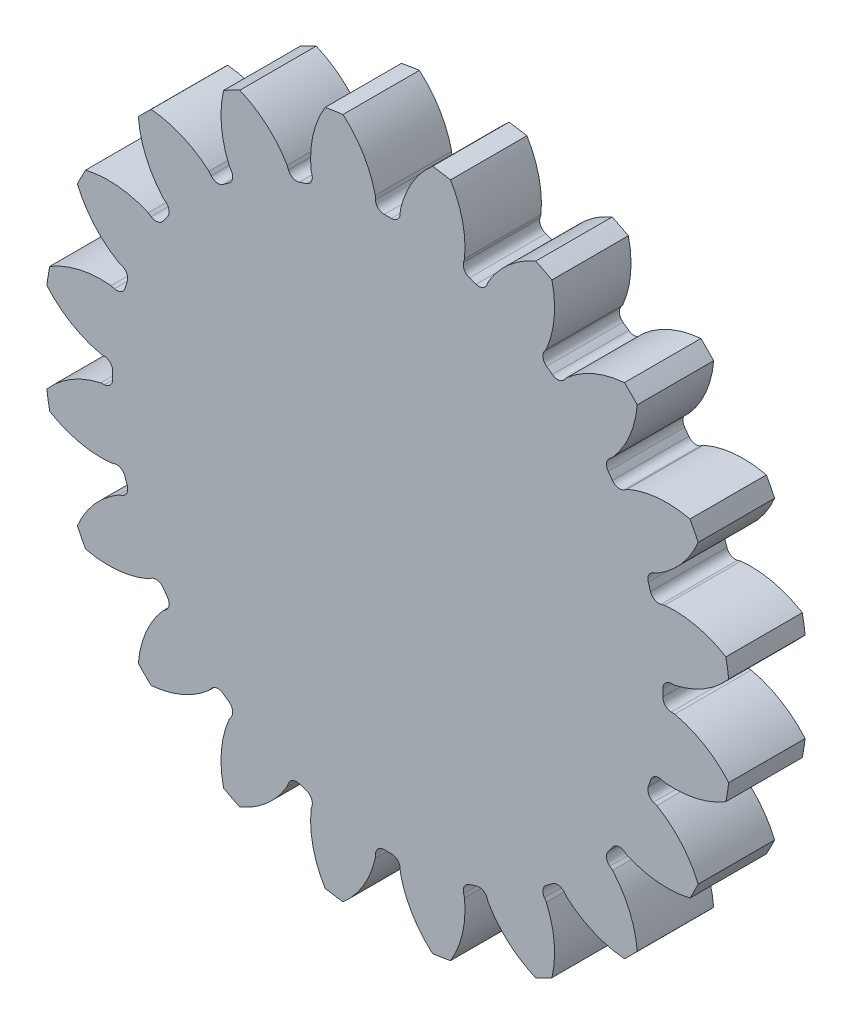
SolidWorks part; units mm, degrees
ref_plane "前视基准面" through (0, 0, 0) normal (0, 0, 1) x (1, 0, 0)
ref_plane "上视基准面" through (0, 0, 0) normal (0, 1, 0) x (1, 0, 0)
ref_plane "右视基准面" through (0, 0, 0) normal (1, 0, 0) x (0, 0, -1)
sketch "Sketch1" plane through (0, 0, 0) normal (0, 0, 1) x (1, 0, 0)
  line L0 (0, 0) -> (0, 22.5) construction
  line L1 (0.8204, 18.7759) -> (0, 0) construction
  line L2 (0, 0) -> (7.1927, 17.363) construction
  line L3 (0.8204, 18.7759) -> (0.7857, 17.9828)
  line L4 (0, 0) -> (3.5198, 22.223) construction
  line L6 (-0.8204, 18.7759) -> (-0.7857, 17.9828)
  circle A0 centre (0, 0) radius 20 construction
  circle A2 centre (0, 0) radius 18 construction
  arc A3 (0.8204, 18.7759) -> (2.9326, 22.3081) centre (7.1927, 17.363) cw
  circle A4 centre (0, 0) radius 18.7939 construction
  arc A5 (-0.7857, 17.9828) -> (0.7857, 17.9828) centre (0, 0) cw
  arc A6 (-0.8204, 18.7759) -> (-2.9326, 22.3081) centre (-7.1927, 17.363) ccw
  circle A7 centre (0, 0) radius 22.5
  arc A8 (1.2061, 19.9636) -> (3.1287, 19.7538) centre (0, 0) cw construction
  dimension "Db" = 37.5877
  dimension "Da" = 45
  dimension "Dp" = 40
  dimension "Dd" = 36
  dimension "alpha" = 20
  dimension "deg_half" = 9
  dimension "s_half" = 1.9348
extrude "Df circle" add sketch "Sketch1" along normal mid plane 5 contours A7
extrude "one teeth" cut sketch "Sketch" against normal through all both and the other way through all contours L3 A3 region at (0, 20.7613, 0)
sketch "Sketch" plane through (0, 0, 0) normal (0, 0, 1) x (1, 0, 0) same geometry as "Sketch1"
fillet "Fillet1" radius 0.57 2 edges at (-0.7857, 17.9828, 0) (0.7857, 17.9828, 0)
pattern_circular "CirPattern1" count 20 over 360 about axis through (0, 0, -2.5) along (0, 0, 1) of "Fillet1", "one teeth" reverse direction yes
equation "\"m\"=1.5"
equation "\"D1@Fillet1\"=\"m\"*0.38"
